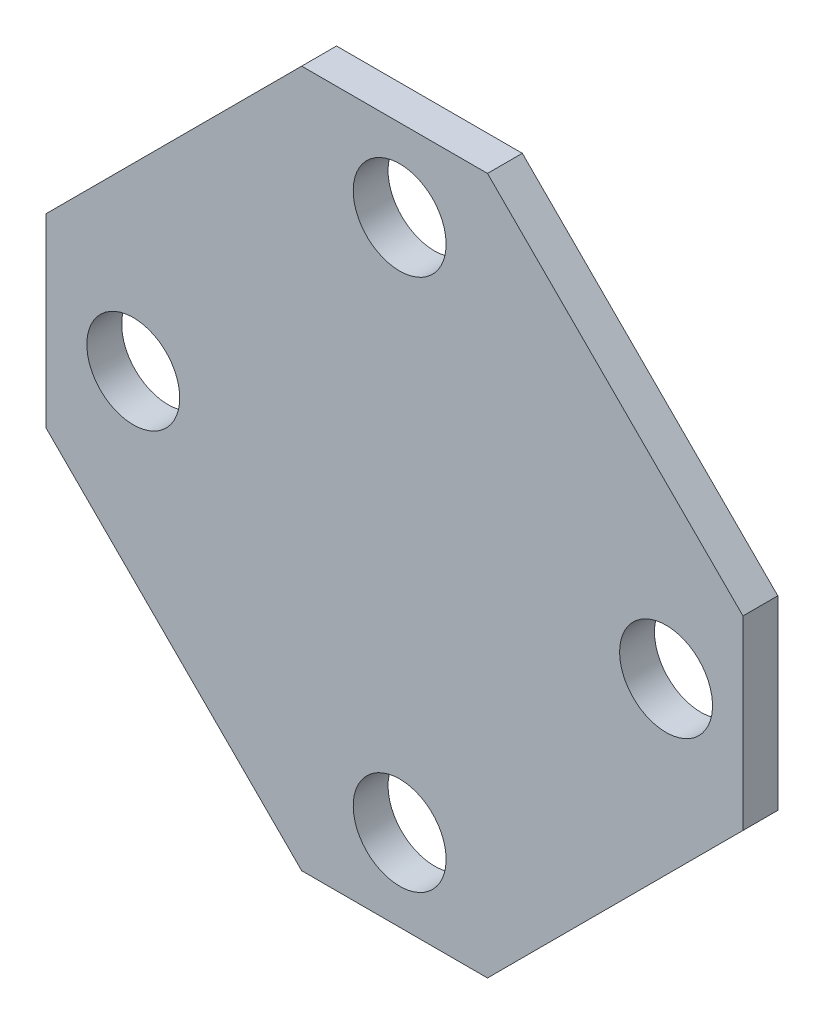
SolidWorks part; units mm, degrees
note: The reader was unsure of these and kept them because the rebuilt part matched: shared geometry of "Sketch1<3>".
ref_plane "Front Plane" through (0, 0, 0) normal (0, 0, 1) x (1, 0, 0)
ref_plane "Top Plane" through (0, 0, 0) normal (0, 1, 0) x (1, 0, 0)
ref_plane "Right Plane" through (0, 0, 0) normal (1, 0, 0) x (0, 0, -1)
sketch "Sketch1" plane through (0, 0, 0) normal (0, 0, 1) x (1, 0, 0)
  line L0 (-8, 30) -> (-30, 8)
  line L1 (8, -30) -> (-8, -30)
  line L2 (30, -8) -> (30, 8)
  line L3 (8, 30) -> (-8, 30)
  line L4 (-30, -8) -> (-30, 8)
  line L5 (30, -30) -> (-30, 30) construction
  line L6 (30, 30) -> (-30, -30) construction
  line L7 (-8, -30) -> (-30, -8)
  line L8 (8, -30) -> (30, -8)
  line L9 (30, 8) -> (8, 30)
  circle A0 centre (-22.5, 0) radius 4
  point P0 (0, 0)
  dimension "D2" = 8
  dimension "D1" = 60
  dimension "D3" = 22.5
extrude "Boss-Extrude2" add sketch "Sketch1" along normal blind 3 contours L0 L4 L7 L1 L8 L2 L9 L3
extrude "Cut-Extrude1" cut sketch "Sketch1<3>" along normal through all contours A0
sketch "Sketch1<3>" plane through (0, 0, 0) normal (0, 0, 1) x (1, 0, 0) same geometry as "Sketch1"
pattern_circular "CirPattern4" count 4 over 360 about axis through (0.4381, 0, 0) along (0, 0, 1) of "Cut-Extrude1"
